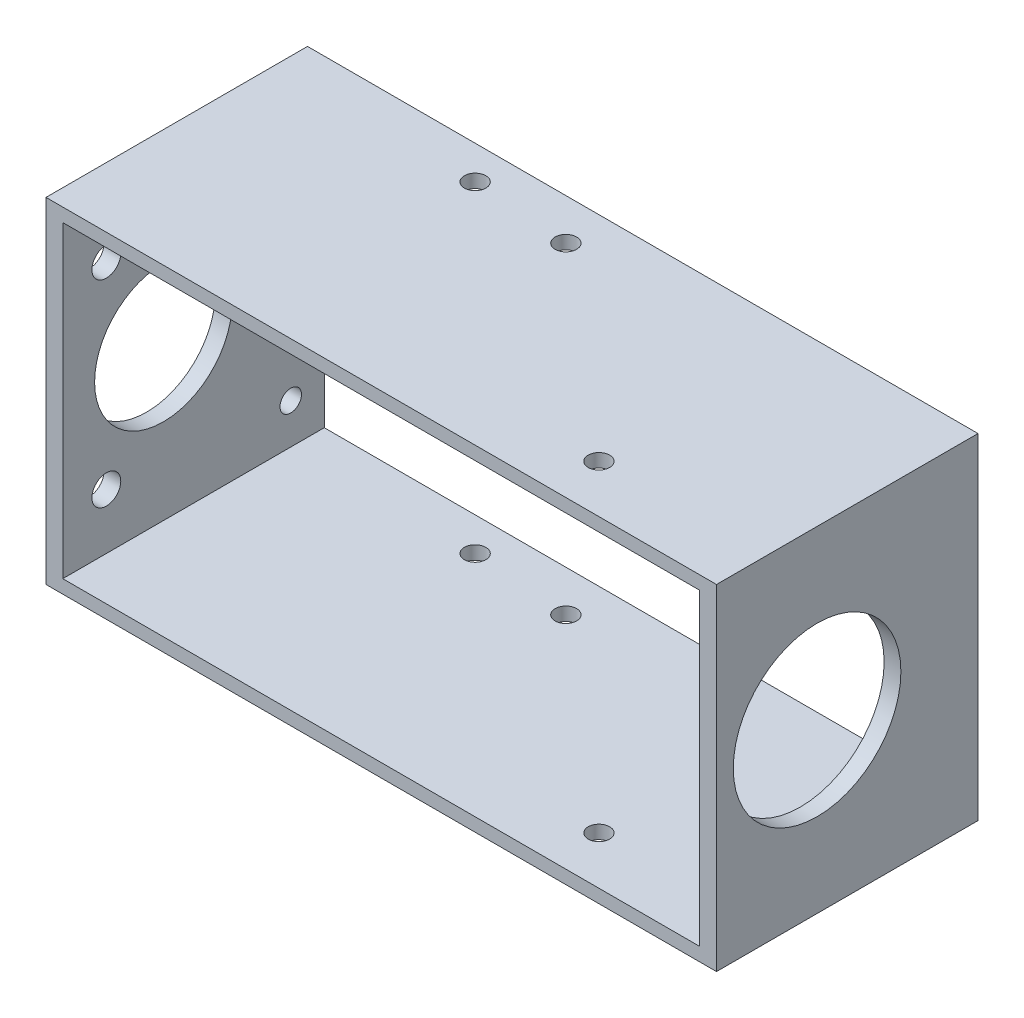
SolidWorks part; units mm, degrees
ref_plane "正面" through (0, 0, 0) normal (0, 0, 1) x (1, 0, 0)
ref_plane "平面" through (0, 0, 0) normal (0, 1, 0) x (1, 0, 0)
ref_plane "右側面" through (0, 0, 0) normal (1, 0, 0) x (0, 0, -1)
sketch "ｽｹｯﾁ1" plane through (0, 0, 0) normal (0, 0, 1) x (1, 0, 0)
  line L1 (-50, -25) -> (50, -25)
  line L2 (-50, -25) -> (-50, 25)
  line L3 (-50, 25) -> (50, 25)
  line L4 (50, -25) -> (50, 25)
  line L5 (-50, -25) -> (50, 25) construction
  line L6 (-50, 25) -> (50, -25) construction
  line L7 (-47.5, -23) -> (47.5, -23)
  line L8 (-47.5, -23) -> (-47.5, 23)
  line L9 (-47.5, 23) -> (47.5, 23)
  line L10 (47.5, -23) -> (47.5, 23)
  line L11 (-47.5, -23) -> (47.5, 23) construction
  line L12 (-47.5, 23) -> (47.5, -23) construction
  point P0 (0, 0)
  point P6 (0, 0)
  dimension "D1" = 2
  dimension "D2" = 2.5
  dimension "D3" = 50
  dimension "D4" = 100
extrude "ﾎﾞｽ - 押し出し1" add sketch "ｽｹｯﾁ1" along normal mid plane 39
sketch "ｽｹｯﾁ2" plane through (0, 25, 0) normal (0, 1, 0) x (1, 0, 0)
  line L0 (-5.3209, 13.3558) -> (25.3209, -12.3558) construction
  line L1 (10, 0.5) -> (50, 0.5) construction
  line L2 (50, -19.5) -> (50, 19.5) construction
  line L3 (50, -19.5) -> (-50, -19.5) construction
  line L4 (-50, -19.5) -> (-50, 19.5) construction
  line L5 (50, 19.5) -> (-50, 19.5) construction
  circle A0 centre (-5.3209, 13.3558) radius 1.6
  circle A1 centre (25.3209, -12.3558) radius 1.6
  circle A2 centre (-20, 14.5) radius 1.6
  dimension "D2" = 3.2
  dimension "D6" = 30
  dimension "D7" = 5
  dimension "D1" = 40
  dimension "D3" = 20
  dimension "D4" = 40
  dimension "D5" = 40
extrude "ｶｯﾄ - 押し出し1" cut sketch "ｽｹｯﾁ2" against normal through all
sketch "ｽｹｯﾁ3" plane through (-50, 0, 0) normal (-1, 0, 0) x (0, 0, 1)
  line L0 (4.5, 0) -> (4.5, 21.5) construction
  line L1 (19.5, 25) -> (19.5, -25) construction
  line L2 (-30.7, -9) -> (-30.7, 9) construction
  line L3 (21.45, 0) -> (-21.45, 0) construction
  line L4 (-12.5, 0) -> (4.5, 0) construction
  line L5 (-14.5, -17) -> (-14.5, 17) construction
  line L6 (19.5, 25) -> (-19.5, 25) construction
  line L7 (-19.5, 25) -> (-19.5, -25) construction
  circle A0 centre (4.5, 0) radius 21.5 construction
  circle A1 centre (4.5, 0) radius 10.25
  circle A3 centre (-30.7, 0) radius 6.05 construction
  circle A4 centre (-30.7, -9) radius 1.6 construction
  circle A5 centre (-30.7, 9) radius 1.6 construction
  circle A8 centre (-12.5, 0) radius 2.15
  circle A9 centre (4.5, 0) radius 17 construction
  circle A10 centre (13, 14.7224) radius 2.15
  circle A11 centre (13, -14.7224) radius 2.15
  circle A12 centre (-14.5, -17) radius 1.6
  circle A13 centre (-14.5, 17) radius 1.6
  point P12 (-30.7, 0)
  point P18 (-14.5, 0)
  point P21 (4.5, 0)
  point P28 (4.5, 0)
  dimension "D1" = 43
  dimension "D3" = 20.5
  dimension "D6" = 3.2
  dimension "D8" = 12.1
  dimension "D4" = 4.3
  dimension "D10" = 34
  dimension "D2" = 3.2
  dimension "D5" = 15
  dimension "D7" = 18
  dimension "D9" = 35.2
  dimension "D12" = 8
  dimension "D13" = 5
  dimension "D11" = 3
extrude "ｶｯﾄ - 押し出し2" cut sketch "ｽｹｯﾁ3" against normal up to next
sketch "ｽｹｯﾁ4" plane through (50, 0, 0) normal (1, 0, 0) x (0, 0, -1)
  circle A0 centre (-4.5, 0) radius 12.5
  circle A1 centre (-4.5, 0) radius 10.25 construction
  dimension "D1" = 25
extrude "ｶｯﾄ - 押し出し3" cut sketch "ｽｹｯﾁ4" against normal up to next
equation "\"D9@ｽｹｯﾁ3\"=(66+22)*0.8/2"
